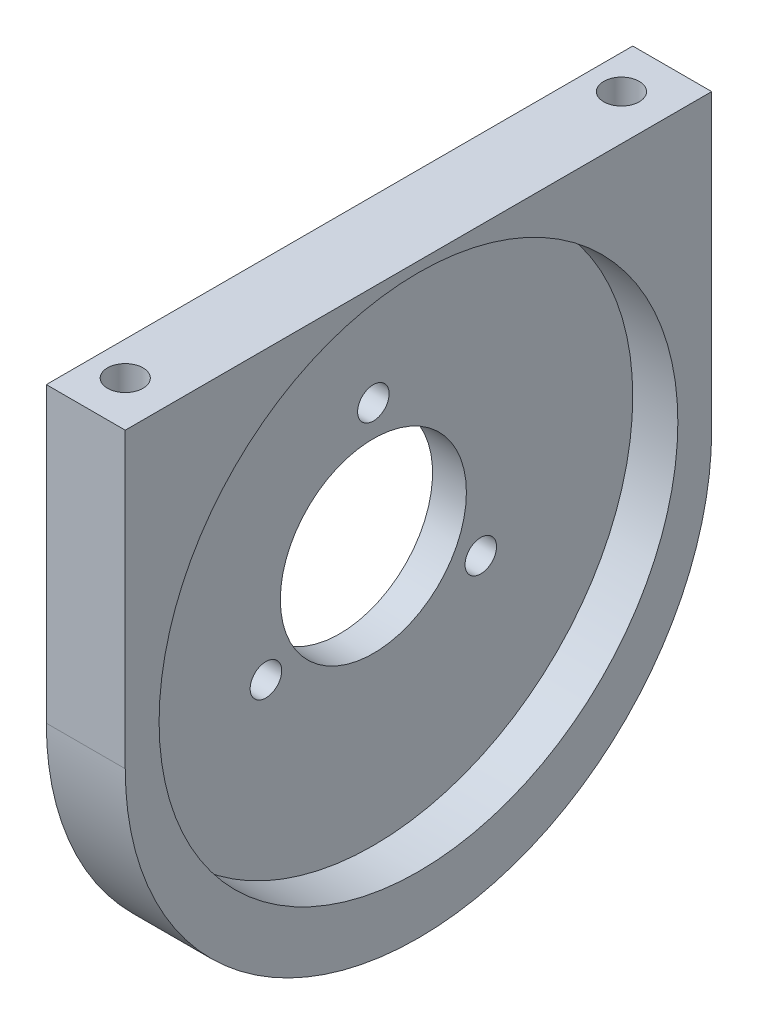
SolidWorks part; units mm, degrees
ref_plane "Plano frontal" through (0, 0, 0) normal (0, 0, 1) x (1, 0, 0)
ref_plane "Plano superior" through (0, 0, 0) normal (0, 1, 0) x (1, 0, 0)
ref_plane "Plano direito" through (0, 0, 0) normal (1, 0, 0) x (0, 0, -1)
sketch "Esboço1" plane through (0, 0, 0) normal (1, 0, 0) x (0, 0, -1)
  line L1 (0, 0) -> (52, 0)
  line L2 (0, 0) -> (0, 52)
  line L3 (0, 52) -> (52, 52)
  line L4 (52, 0) -> (52, 52)
  dimension "D1" = 52
  dimension "D2" = 52
extrude "Ressalto-extrusão1" add sketch "Esboço1" along normal blind 7
sketch "Esboço2" plane through (0, 0, 0) normal (-1, 0, 0) x (0, 0, 1)
  line L1 (-26, 52) -> (-26, 28.1)
  line L2 (-52, 52) -> (0, 52) construction
  circle A0 centre (-26, 28.1) radius 8.25
  dimension "D1" = 16.5
  dimension "D3" = 23.9
extrude "Corte-extrusão1" cut sketch "Esboço2" against normal through all contours A0
sketch "Esboço6" plane through (0, 0, 0) normal (-1, 0, 0) x (0, 0, 1)
  line L1 (-26, 52) -> (-26, 39.1)
  line L2 (-52, 52) -> (0, 52) construction
  circle A0 centre (-26, 28.1) radius 8.25 construction
  point P0 (-26, 39.1)
  dimension "D1" = 11
hole_wizard "Escareado para parafuso de máquina com cabeça chata (100) de #32" positions "Esboço13" profile "Esboço14" countersink size "#3" standard "Ansi Inch" end condition up to next
sketch "Esboço13" plane through (0, 0, 0) normal (-1, 0, 0) x (0, 0, 1)
  point P0 (-26, 39.1)
sketch "Esboço14" plane through (0, 39.1, -26) normal (0, 1, 0) x (0, 0, 1)
  line L0 (0, 0) -> (0, 7)
  line L1 (0, 7) -> (1.397, 7)
  line L2 (1.397, 7) -> (1.397, 0.9484)
  line L3 (1.397, 0.9484) -> (2.5273, 0)
  line L5 (2.5273, 0) -> (0, 0)
  line L6 (-1.397, 0.9484) -> (-2.5273, 0) construction
  line L11 (0, -6.35) -> (0, 107.95) construction
  dimension "Thru Hole Dia." = 2.794
  dimension "Thru Hole Depth" = 7
  dimension "Near C'Sink Dia." = 5.0546
  dimension "Near C'Sink Angle" = 100
pattern_circular "PadrãoCircular1" count 3 over 360 about axis through (0, 28.1, -26) along (-1, 0, 0) of "Escareado para parafuso de máquina com cabeça chata (100) de #32"
sketch "Esboço27" plane through (7, 0, 0) normal (1, 0, 0) x (0, 0, -1)
  circle A0 centre (26, 28.1) radius 23
  dimension "D1" = 46
extrude "Corte-extrusão5" cut sketch "Esboço27" against normal blind 4
fillet "Filete1" radius 26 2 edges at (3.5, 0, -52) (3.5, 0, 0)
hole_wizard "Furo roscado para conduíte de M3x0.51" positions "Esboço33" profile "Esboço34" tap size "M3x0.5" standard "Helicoil® Metric"
sketch "Esboço33" plane through (0, 52, 0) normal (0, 1, 0) x (1, 0, 0)
  line L0 (0, 52) -> (0, 0) construction
  line L1 (7, 52) -> (0, 52) construction
  line L2 (7, 0) -> (0, 0) construction
  point P0 (3, 48)
  point P2 (3, 4)
  dimension "D1" = 3
  dimension "D2" = 4
  dimension "D3" = 3
  dimension "D4" = 4
cosmetic thread "Rosca de furo1" parameters "D1"=10, "D2"=3.716
cosmetic thread "Rosca de furo2" parameters "D1"=10, "D2"=3.716
sketch "Esboço34" plane through (3, 52, -48) normal (1, 0, 0) x (0, 0, 1)
  line L0 (0, 0) -> (0, 10.9464)
  line L1 (0, 10.9464) -> (1.575, 10)
  line L2 (1.575, 10) -> (1.575, 0)
  line L5 (1.575, 0) -> (0, 0)
  line L10 (0, 10.9464) -> (-1.575, 10) construction
  line L11 (0, -6.35) -> (0, 107.95) construction
  dimension "Tap Drill Dia." = 3.15
  dimension "Tap Drill Depth" = 10
  dimension "Drill Angle" = 118
